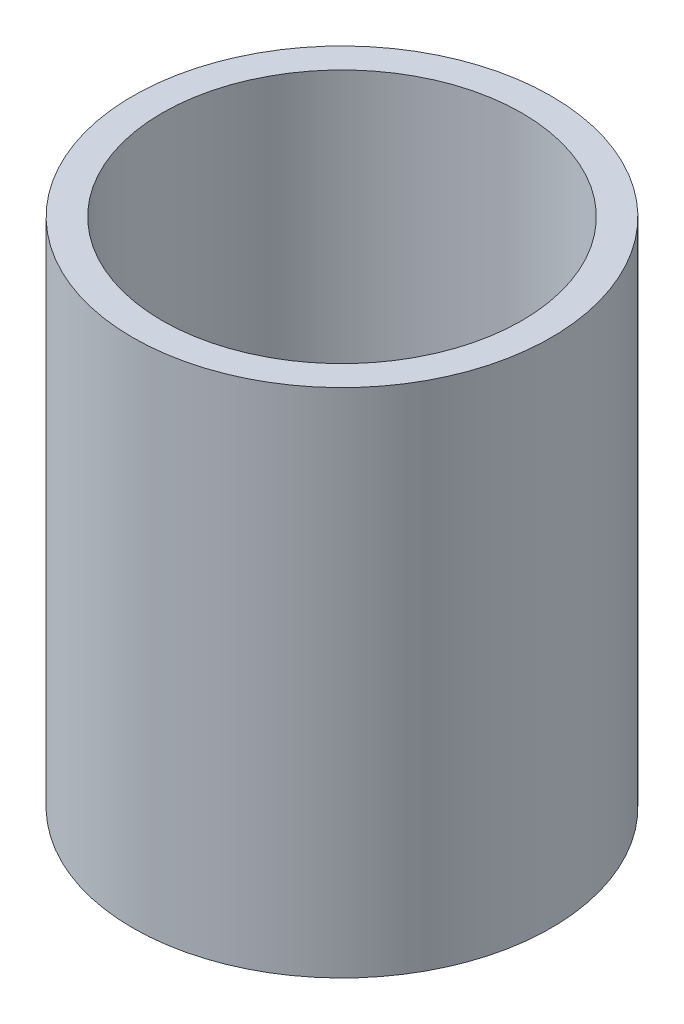
SolidWorks part; units mm, degrees
ref_plane "Front Plane" through (0, 0, 0) normal (0, 0, 1) x (1, 0, 0)
ref_plane "Top Plane" through (0, 0, 0) normal (0, 1, 0) x (1, 0, 0)
ref_plane "Right Plane" through (0, 0, 0) normal (1, 0, 0) x (0, 0, -1)
sketch "Sketch1" plane through (0, 0, 0) normal (0, 1, 0) x (1, 0, 0)
  circle A0 centre (0, 0) radius 25
  dimension "SLEEVE_OD" = 50
extrude "Boss-Extrude1" add sketch "Sketch1" along normal blind 61.0964
sketch "Sketch2" plane through (0, 0, 0) normal (0, 1, 0) x (1, 0, 0)
  circle A0 centre (0, 0) radius 21.4916
  dimension "BORE_D" = 42.9832
extrude "Cut-Extrude1" cut sketch "Sketch2" along normal through all
chamfer "Chamfer1" distance 2.5164 angle 30 rebuild error yes
